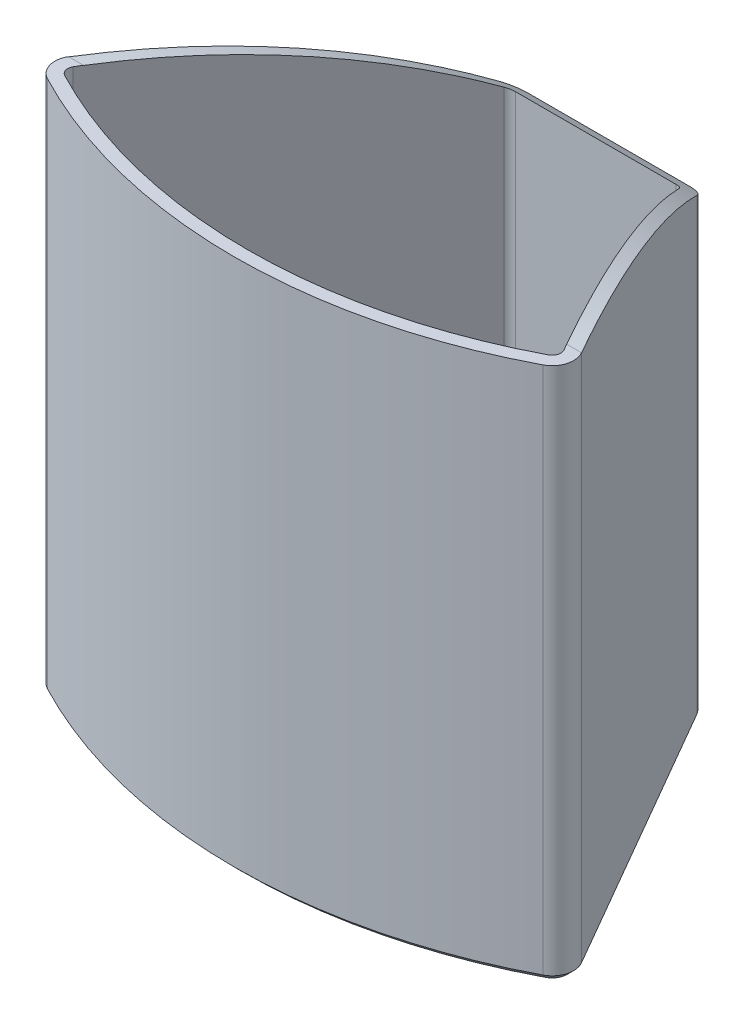
SolidWorks part; units mm, degrees
ref_plane "前视基准面" through (0, 0, 0) normal (0, 0, 1) x (1, 0, 0)
ref_plane "上视基准面" through (0, 0, 0) normal (0, 1, 0) x (1, 0, 0)
ref_plane "右视基准面" through (0, 0, 0) normal (1, 0, 0) x (0, 0, -1)
other "Configuration Table"
sketch "草图1" plane through (0, 0, 0) normal (0, 1, 0) x (1, 0, 0)
  circle A0 centre (0, 0) radius 50
  dimension "D1" = 100
extrude "凸台-拉伸1" add sketch "草图1" along normal blind 50
sketch "草图2" plane through (0, 50, 0) normal (0, 1, 0) x (1, 0, 0)
  line L0 (-50, 0) -> (50, 0)
  line L1 (25, 43.3013) -> (-25, -43.3013)
  line L2 (25, -43.3013) -> (-25, 43.3013)
  circle A1 centre (0, 0) radius 50
  circle A2 centre (0, 0) radius 50
  point P11 (0, 0)
  circle M3 centre (0, 0) radius 50
  dimension "D1" = 0
  dimension "D2" = 3
extrude "切除-拉伸2" cut sketch "草图2" against normal through all contours L2 L1 M3 | L1 L0 M3 | L2 L0 M3 | L0 L2 M3 | L1 L0 M3 region at (-27.5664, 50, -15.9155) region at (-27.5664, 50, 15.9155) region at (27.5664, 50, -15.9155) region at (0, 50, -31.831) region at (27.5664, 50, 15.9155)
sketch "草图3" plane through (0, 50, 0) normal (0, 1, 0) x (1, 0, 0)
  line L0 (-8.6603, -15) -> (8.6603, -15)
  line L1 (0, 0) -> (-25, -43.3013) construction
  line L2 (25, -43.3013) -> (0, 0) construction
  line L5 (25, -43.3013) -> (0, 0)
  line L6 (0, 0) -> (-25, -43.3013)
  line L7 (25, -43.3013) -> (0, 0)
  line L8 (0, 0) -> (-25, -43.3013)
  circle A0 centre (0, 0) radius 15
  arc A2 (-25, -43.3013) -> (25, -43.3013) centre (0, 0) ccw
  arc A3 (-25, -43.3013) -> (25, -43.3013) centre (0, 0) ccw
  line M2 (25, -43.3013) -> (0, 0)
  line M3 (0, 0) -> (-25, -43.3013)
  dimension "D1" = 30
  dimension "D2" = 0
extrude "切除-拉伸3" cut sketch "草图3" against normal through all contours A0 L7 M3 | A0 L0 M2 | A0 L8 L0 region at (-6.0821, 50, 14.3903) region at (6.0821, 50, 14.3903) region at (0, 50, 9.5493)
fillet "圆角1" radius 2 4 edges at (-8.6603, 25, 15) (-25, 25, 43.3013) (25, 25, 43.3013) (8.6603, 25, 15)
chamfer "倒角1" distance 0.6 angle 45 8 edges at (0, 0, 15) (-8.5056, 0, 15.2679) (8.5056, 0, 15.2679) (-16.6084, 0, 28.7666) (16.6084, 0, 28.7666) (-24.1678, 0, 43.0909) (24.1678, 0, 43.0909) (0, 0, 50)
shell "抽壳1" thickness 1.2 removed face at (0, 50, 29.9064)
sketch "草图4" plane through (0, 0, 0) normal (1, 0, 0) x (0, 0, -1)
  line L0 (-16.3, 0) -> (-41.8331, 0) construction
  line L1 (-44.5, -3) -> (-44.5, 0)
  line L2 (-49.4, 0) -> (-43.7737, 0) construction
  line L3 (-41.5, -3) -> (-41.5, 0)
  line L4 (-43.7737, 0) -> (-41.8331, 0) construction
  line L5 (-44.5, 0) -> (-41.5, 0)
  circle A0 centre (-43, -3) radius 1.5
  dimension "D2" = 3
  dimension "D1" = 43
  dimension "D3" = 3
extrude "凸台-拉伸2" add sketch "草图4" along normal blind 2 and the other way blind 2 contours A0 L3 L5 L1 | A0 region at (0, -0.9417, 43) region at (0, -3, 43)
sketch "草图5" plane through (2, 0, 0) normal (1, 0, 0) x (0, 0, -1)
  circle A0 centre (-43, -3) radius 1.5
  arc A1 (-44.5, -3) -> (-41.5, -3) centre (-43, -3) ccw construction
extrude "凸台-拉伸3" add sketch "草图5" along normal blind 3
mirror "镜向1" about plane through (0, 0, 0) normal (1, 0, 0) of "凸台-拉伸3"
sketch "草图6" plane through (0, 0, 0) normal (1, 0, 0) x (0, 0, -1)
  line L0 (-41.5331, 50) -> (-16, 50) construction
  line L1 (-41.5331, 50) -> (-16, 50) construction
  line L2 (-16, 0.6) -> (-15, 0.6) construction
  line L3 (-15, 0.6) -> (-15, 50) construction
  line L4 (-15, 50) -> (-16, 50) construction
  line L5 (-41.5331, 50) -> (-41.5331, 0.6) construction
  line L6 (-41.5331, 0.6) -> (-16, 0.6) construction
  line L7 (-16, 50) -> (-41.5331, 50) construction
  line L8 (-16, 0.6) -> (-15, 0.6)
  line L9 (-15, 0.6) -> (-15, 50)
  line L10 (-15, 50) -> (-16, 50)
  line L11 (-41.5331, 50) -> (-41.5331, 0.6)
  line L12 (-41.5331, 0.6) -> (-16, 0.6)
  line L13 (-16, 50) -> (-41.5331, 50)
  circle A0 centre (-43, -3) radius 53
extrude "切除-拉伸4" cut sketch "草图6" against normal through all and the other way through all contours A0 L9 L10 L13 L11 region at (0, 47.6343, 21.8872)
sketch "草图7" plane through (0, 1.2, 0) normal (0, 1, 0) x (1, 0, 0)
  line L0 (2, -44.5) -> (2, -41.5) construction
  line L1 (2, -44.5) -> (2, -41.5) construction
  line L2 (-2, -44.5) -> (-2, -41.5) construction
  line L3 (-2, -44.5) -> (-2, -41.5) construction
  line L5 (-2, -41.5) -> (2, -41.5)
  line L6 (-2, -41.5) -> (-2, -44.5)
  line L7 (-2, -44.5) -> (2, -44.5)
  line L8 (2, -41.5) -> (2, -44.5)
  line L9 (-3.3, -40.2) -> (3.3, -40.2)
  line L10 (-3.3, -40.2) -> (-3.3, -45.8)
  line L11 (-3.3, -45.8) -> (3.3, -45.8)
  line L12 (3.3, -40.2) -> (3.3, -45.8)
  dimension "D1" = 1.3
  dimension "D2" = 1.3
  dimension "D3" = 1.3
  dimension "D4" = 1.3
extrude "凸台-拉伸4" add sketch "草图7" along normal blind 2.2
sketch "草图8" plane through (0, 1.2, 0) normal (0, 1, 0) x (1, 0, 0)
  line L4 (2, -44.5) -> (2, -41.5)
  line L5 (2, -41.5) -> (-2, -41.5)
  line L6 (-2, -41.5) -> (-2, -44.5)
  line L7 (-2, -44.5) -> (2, -44.5)
  line L8 (2, -44.5) -> (2, -41.5)
  line L9 (2, -41.5) -> (-2, -41.5)
  line L10 (-2, -41.5) -> (-2, -44.5)
  line L11 (-2, -44.5) -> (2, -44.5)
  dimension "D1" = 0
extrude "切除-拉伸7" cut sketch "草图8" against normal up to surface (1.2 mm away) up to face at (0, 0, 30.0694)
sketch "草图9" plane through (0, 0, 0) normal (0, -1, 0) x (1, 0, 0)
  line L1 (-26.2613, 50.0408) -> (22.6303, 50.0408)
  line L2 (-26.2613, 50.0408) -> (-26.2613, 35.3058)
  line L3 (-26.2613, 35.3058) -> (22.6303, 35.3058)
  line L4 (22.6303, 50.0408) -> (22.6303, 35.3058)
extrude "切除-拉伸8" cut sketch "草图9" along normal through all
chamfer "倒角2" distance 0.4 angle 45 4 edges at (2, 0, 43) (0, 0, 41.5) (-2, 0, 43) (0, 0, 44.5)
sketch "草图10" plane through (0, 3.4, 0) normal (0, 1, 0) x (1, 0, 0)
  line L0 (-2.1, -41.4) -> (2.1, -41.4)
  line L1 (-2, -41.5) -> (2, -41.5)
  line L2 (-2, -41.5) -> (-2, -44.5)
  line L3 (-2, -44.5) -> (2, -44.5)
  line L4 (2, -41.5) -> (2, -44.5)
  line L5 (2.1, -41.4) -> (2.1, -44.6)
  line L6 (-2.1, -44.6) -> (2.1, -44.6)
  line L7 (-2.1, -41.4) -> (-2.1, -44.6)
  dimension "D1" = 0.1
extrude "切除-拉伸9" cut sketch "草图10" against normal through all
sketch "草图11" plane through (0, 3.4, 0) normal (0, 1, 0) x (1, 0, 0)
  line L4 (-3.3, -40.2) -> (-3.3, -45.8)
  line L5 (-3.3, -45.8) -> (3.3, -45.8)
  line L6 (3.3, -45.8) -> (3.3, -40.2)
  line L7 (3.3, -40.2) -> (-3.3, -40.2)
  line L8 (-3.3, -40.2) -> (-3.3, -45.8)
  line L9 (-3.3, -45.8) -> (3.3, -45.8)
  line L10 (3.3, -45.8) -> (3.3, -40.2)
  line L11 (3.3, -40.2) -> (-3.3, -40.2)
  dimension "D1" = 0
extrude "凸台-拉伸5" add sketch "草图11" along normal blind 1.2
